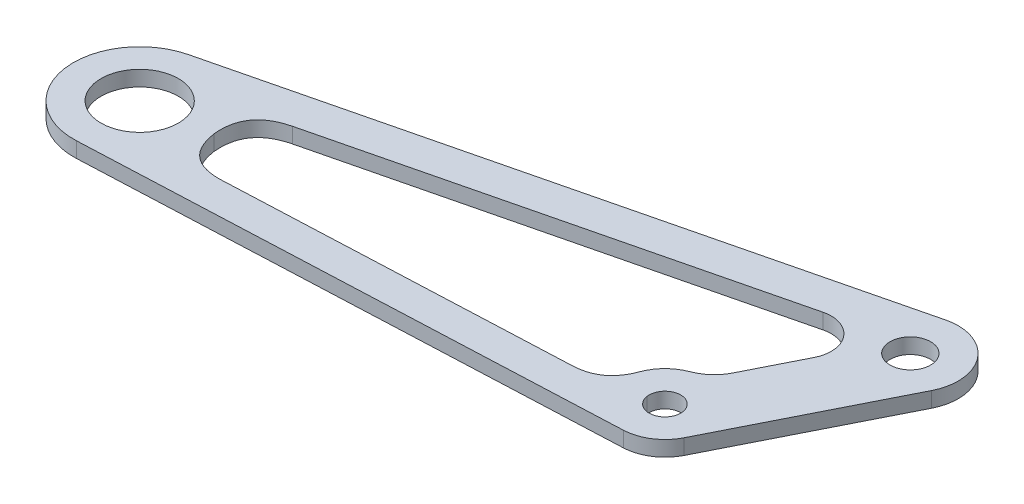
SolidWorks part; units mm, degrees
material "6061-T6 (SS)"
ref_plane "Front Plane" through (0, 0, 0) normal (0, 0, 1) x (1, 0, 0)
ref_plane "Top Plane" through (0, 0, 0) normal (0, 1, 0) x (1, 0, 0)
ref_plane "Right Plane" through (0, 0, 0) normal (1, 0, 0) x (0, 0, -1)
sketch "Sketch1" plane through (0, 0, 0) normal (0, 1, 0) x (1, 0, 0)
  line L0 (0, 0) -> (124.8778, 34.4406) construction
  line L1 (124.8778, 34.4406) -> (108.585, 0) construction
  line L2 (108.585, 0) -> (0, 0) construction
  line L3 (-3.2545, 13.3112) -> (122.5251, 44.0632)
  line L5 (116.6057, -4.036) -> (133.7266, 29.9879)
  line L6 (108.585, 0) -> (109.8191, -8.8937) construction
  line L7 (-1.8972, 7.7597) -> (123.8824, 38.5117)
  line L8 (111.5006, -1.4671) -> (128.6215, 32.5568)
  line L9 (0.3476, -7.9807) -> (108.727, -3.2608)
  line L10 (108.585, 0) -> (80.8924, 28.001) construction
  line L11 (108.585, 0) -> (108.585, 29.9472) construction
  line L12 (74.1772, 26.3592) -> (50.5928, -5.7926) construction
  line L13 (78.0157, 27.2977) -> (53.8469, -5.6508)
  line L14 (70.3387, 25.4208) -> (47.3388, -5.9343)
  line L15 (78.0157, 27.2977) -> (100.7231, 4.3373)
  line L16 (83.7692, 28.7044) -> (104.3351, 7.9094)
  line L17 (62.385, 10.2833) -> (60.3369, 11.7857) construction
  line L18 (62.385, 10.2833) -> (64.4331, 8.781) construction
  line L19 (94.7387, 14.0005) -> (92.9327, 12.2144) construction
  line L20 (94.7387, 14.0005) -> (96.5447, 15.7866) construction
  line L21 (108.223, 8.9716) -> (117.6372, 27.6802)
  line L22 (0.5962, -13.6903) -> (108.9757, -8.9704)
  line L23 (10.4829, 8.8255) -> (114.972, 34.3721)
  line L24 (12.2244, -6.1923) -> (99.9253, -2.3729)
  line L25 (116.849, 3.5109) -> (127.6235, 24.9227)
  circle A0 centre (0, 0) radius 7.9883
  circle A1 centre (124.8778, 34.4406) radius 4.191
  circle A2 centre (108.585, 0) radius 3.2639
  circle A3 centre (0, 0) radius 13.7033
  circle A4 centre (108.585, 0) radius 8.9789
  circle A5 centre (124.8778, 34.4406) radius 9.906
  arc A6 (-3.2545, 13.3112) -> (6.558, -12.0322) centre (0, 0) ccw
  arc A7 (116.6057, -4.036) -> (108.585, -8.9789) centre (108.585, 0) cw
  arc A8 (122.5251, 44.0632) -> (133.7266, 29.9879) centre (124.8778, 34.4406) cw
  circle A9 centre (109.9941, 26.618) radius 6.35
  dimension "D4" = 15.9766
  dimension "D5" = 6.5278
  dimension "D6" = 8.382
  dimension "D7" = 5.715
  dimension "D8" = 5.715
  dimension "D9" = 5.715
  dimension "D18" = 12.7
  dimension "D1" = 129.54
  dimension "D2" = 38.1
  dimension "D3" = 108.585
  dimension "D10" = 97.9
  dimension "D11" = 70
  dimension "D12" = 40
  dimension "D13" = 5.08
  dimension "D14" = 7.62
  dimension "D15" = 1.905
  dimension "D16" = 1.27
  dimension "D17" = 2.54
extrude "Boss-Extrude4" add sketch "Sketch1" against normal blind 3.175 contours A5 L7 A1 L8 | A5 L3 A3 L7 | A3 L9 A0 L7 | L9 A3 L7 A0 | A3 L23 L14 L7 | A3 L9 L14 L24 | A4 L9 A3 L22 | A4 L24 L13 L9 | L24 L14 L9 L13 | L14 L23 L13 L7 | L15 L23 L16 L7 | A5 L7 L16 L23 | L13 L23 L15 | L7 A5 L8 A1 | A4 L8 A2 L9 | L8 A4 L9 A2 | A5 L21 A4 L8 | A5 L8 A4 L25 | A5 L25 A4 L5 | A9 A5 L23 region at (3.0968, 0, -12.9665) region at (60.9475, 0, -26.1319) region at (130.8221, 0, -42.0134) region at (55.5151, 0, 8.5135) region at (9.0449, 0, -1.2899) region at (39.5989, 0, -16.9337) region at (99.788, 0, -31.6497) region at (120.3417, 0, -30.8307) region at (110.891, 0, 3.5657) region at (73.3007, 0, -25.1644) region at (123.7822, 0, -13.5289) region at (81.6734, 0, -27.2114) region at (114.536, 0, -31.1624) region at (29.8427, 0, 6.06) region at (77.952, 0, -25.9747) region at (121.1077, 0, -14.7315) region at (116.4352, 0, -16.8286) region at (106.419, 0, -3.3492) region at (77.2289, 0, 4.0002) region at (51.0744, 0, 5.136)
ref_plane "Plane1" through (108.585, 0, 0) normal (0.1374, 0, 0.9905) x (0.9905, 0, -0.1374)
split line "Split Line1"
sketch "Sketch2" [suppressed] plane through (0, -3.175, 0) normal (0, -1, 0) x (1, 0, 0)
  line L1 (69.4473, -23.6659) -> (60.7288, -1.2641)
  line L2 (62.8949, 2.1892) -> (101.6127, 5.2609)
  line L3 (101.2476, -37.8411) -> (79.7056, -31.0891)
  line L4 (79.2148, -26.4545) -> (98.3531, -15.6299)
  line L5 (59.9072, -25.992) -> (7.538, -8.592)
  line L6 (63.0965, -22.7173) -> (54.4829, 1.0899)
  line L7 (51.7805, 2.7463) -> (11.1946, -2.3078)
  line L8 (73.1912, -24.8791) -> (102.155, -6.1958)
  line L9 (104.5239, -35.0732) -> (102.1201, -17.4966)
  circle A0 centre (111.76, 0) radius 11.43 construction
  circle A3 centre (0, 0) radius 11.43 construction
  arc A4 (11.1946, -2.3078) -> (7.538, -8.592) centre (0, 0) cw
  arc A5 (101.6127, 5.2609) -> (102.155, -6.1958) centre (111.76, 0) ccw
  arc A6 (101.2476, -37.8411) -> (104.5239, -35.0732) centre (102.0073, -35.4173) ccw
  arc A7 (98.3531, -15.6299) -> (102.1201, -17.4966) centre (99.6035, -17.8407) cw
  arc A8 (69.4473, -23.6659) -> (73.1912, -24.8791) centre (71.8144, -22.7446) ccw
  arc A9 (60.7288, -1.2641) -> (62.8949, 2.1892) centre (63.0958, -0.3428) cw
  arc A10 (63.0965, -22.7173) -> (59.9072, -25.992) centre (60.7081, -23.5815) cw
  arc A11 (54.4829, 1.0899) -> (51.7805, 2.7463) centre (52.0944, 0.2257) ccw
  arc A12 (79.2148, -26.4545) -> (79.7056, -31.0891) centre (80.4653, -28.6654) ccw
  dimension "D1" = 2.54
  dimension "D2" = 2.54
  dimension "D3" = 2.54
  dimension "D4" = 2.54
  dimension "D5" = 2.54
  dimension "D6" = 2.54
  dimension "D7" = 2.54
extrude "Cut-Extrude2" [suppressed] cut sketch "Sketch2" against normal through all
fillet "Fillet1" radius 8.89 4 edges at (108.223, -1.5875, -8.9716) (10.4829, -1.5875, -8.8255) (99.9253, -1.5875, 2.3729) (12.2244, -1.5875, 6.1923) conic rho 0.5
fillet "Fillet2" [suppressed] radius 3.81
fillet "Fillet3" [suppressed] radius 2.54
equation "\"x\"= .05"
